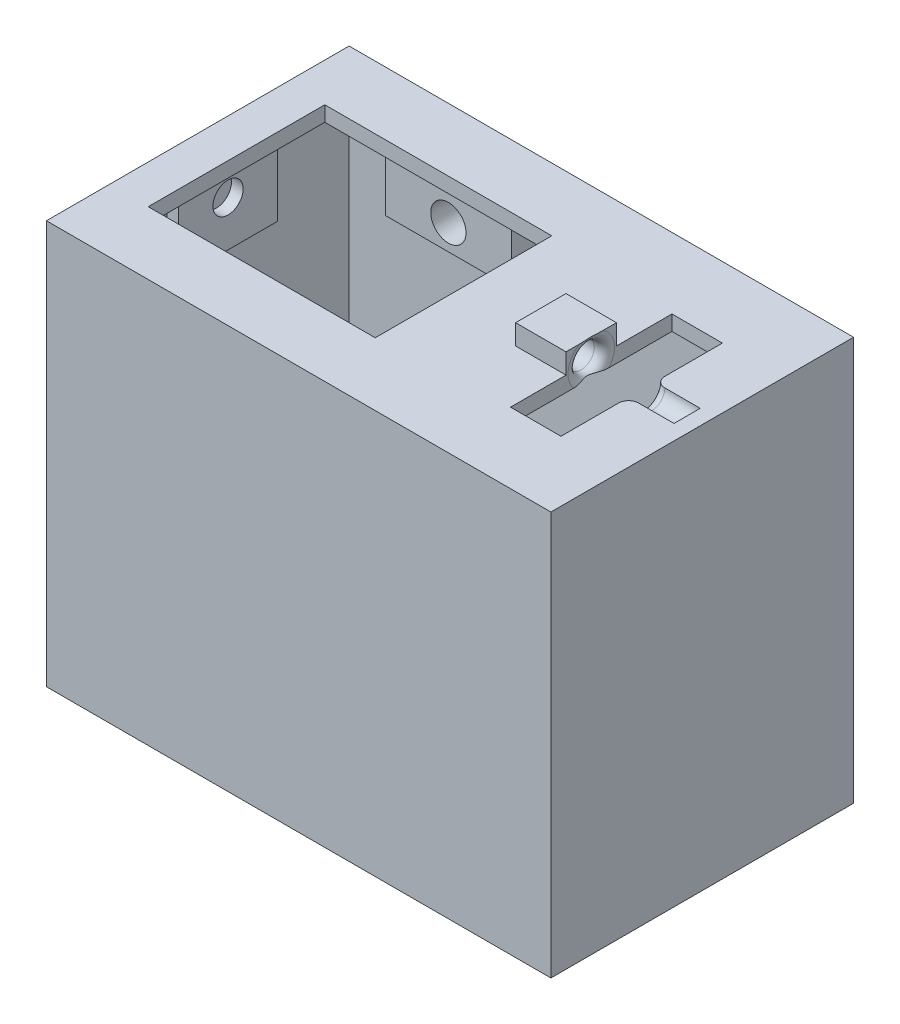
SolidWorks part; units mm, degrees
ref_plane "Front Plane" through (0, 0, 0) normal (0, 0, 1) x (1, 0, 0)
ref_plane "Top Plane" through (0, 0, 0) normal (0, 1, 0) x (1, 0, 0)
ref_plane "Right Plane" through (0, 0, 0) normal (1, 0, 0) x (0, 0, -1)
sketch "Sketch1" plane through (0, 0, 0) normal (0, 1, 0) x (1, 0, 0)
  line L1 (-63.5, -38.1) -> (63.5, -38.1)
  line L2 (-63.5, -38.1) -> (-63.5, 38.1)
  line L3 (-63.5, 38.1) -> (63.5, 38.1)
  line L4 (63.5, -38.1) -> (63.5, 38.1)
  line L5 (-63.5, -38.1) -> (63.5, 38.1) construction
  line L6 (-63.5, 38.1) -> (63.5, -38.1) construction
  point P0 (0, 0)
  dimension "D1" = 127
  dimension "D2" = 76.2
extrude "main body" add sketch "Sketch1" along normal blind 101.6
shell "hollow it" thickness 3.81 removed face at (0, 0, 0)
sketch "Sketch2" plane through (0, 101.6, 0) normal (0, 1, 0) x (1, 0, 0)
  line L0 (63.5, -38.1) -> (63.5, 38.1) construction
  line L1 (48.26, 20.32) -> (35.56, 20.32)
  line L2 (48.26, 20.32) -> (48.26, -20.32)
  line L3 (48.26, -20.32) -> (35.56, -20.32)
  line L4 (35.56, 20.32) -> (35.56, -20.32)
  line L5 (48.26, 20.32) -> (35.56, -20.32) construction
  line L6 (48.26, -20.32) -> (35.56, 20.32) construction
  point P0 (41.91, 0)
  dimension "D1" = 40.64
  dimension "D2" = 12.7
  dimension "D3" = 15.24
extrude "hole for scrollwheel" cut sketch "Sketch2" against normal up to next
ref_plane "arm guys plane" through (35.56, 0, 0) normal (1, 0, 0) x (0, 0, -1)
sketch "Sketch3" plane through (35.56, 0, 0) normal (1, 0, 0) x (0, 0, -1)
  line L0 (0, 101.6) -> (6.35, 101.6)
  line L1 (20.32, 101.6) -> (-20.32, 101.6) construction
  line L2 (6.35, 101.6) -> (6.35, 106.68)
  line L3 (6.35, 106.68) -> (-6.35, 106.68)
  line L4 (-6.35, 106.68) -> (-6.35, 101.6)
  line L5 (-6.35, 101.6) -> (0, 101.6)
  dimension "D1" = 6.35
  dimension "D2" = 6.35
  dimension "D3" = 5.08
extrude "nibble base hole" add sketch "Sketch3" against normal blind 12.7
ref_point "nibble base point"
sketch "Sketch5" plane through (35.56, 0, 0) normal (1, 0, 0) x (0, 0, -1)
  circle A0 centre (0, 101.6) radius 3.302
extrude "nibble hole" cut sketch "Sketch5" against normal blind 11.43 and the other way blind 24.13
fillet "easy to insert scroll wheel" radius 2.54 2 edges at (48.26, 98.298, 0) (35.56, 101.6, 3.302)
sketch "Sketch6" plane through (0, 101.6, 0) normal (0, 1, 0) x (1, 0, 0)
  line L1 (3.4013, 22.225) -> (-53.7487, 22.225)
  line L2 (3.4013, 22.225) -> (3.4013, -22.225)
  line L3 (3.4013, -22.225) -> (-53.7487, -22.225)
  line L4 (-53.7487, 22.225) -> (-53.7487, -22.225)
  line L5 (3.4013, 22.225) -> (-53.7487, -22.225) construction
  line L6 (3.4013, -22.225) -> (-53.7487, 22.225) construction
  point P0 (-25.1737, 0)
  dimension "D1" = 57.15
  dimension "D2" = 44.45
  dimension "D3" = 0
extrude "hole for joystick" cut sketch "Sketch6" against normal blind 11.43
sketch "Sketch10" plane through (0, 97.79, 0) normal (0, -1, 0) x (1, 0, 0)
  line L0 (-59.69, 34.29) -> (59.69, 34.29) construction
  line L1 (-47.3987, 31.75) -> (-2.9487, 31.75)
  line L2 (-47.3987, 31.75) -> (-47.3987, 24.765)
  line L3 (-47.3987, 24.765) -> (-2.9487, 24.765)
  line L4 (-2.9487, 31.75) -> (-2.9487, 24.765)
  line L5 (-47.3987, 31.75) -> (-2.9487, 24.765) construction
  line L6 (-47.3987, 24.765) -> (-2.9487, 31.75) construction
  line L7 (59.69, -34.29) -> (-59.69, -34.29) construction
  line L8 (-41.0487, -31.75) -> (-9.2987, -31.75)
  line L9 (-41.0487, -31.75) -> (-41.0487, -24.765)
  line L10 (-41.0487, -24.765) -> (-9.2987, -24.765)
  line L11 (-9.2987, -31.75) -> (-9.2987, -24.765)
  line L12 (-41.0487, -31.75) -> (-9.2987, -24.765) construction
  line L13 (-41.0487, -24.765) -> (-9.2987, -31.75) construction
  point P0 (-25.1737, 28.2575)
  point P5 (0, 34.29)
  point P10 (-25.1737, -28.2575)
  point P15 (0, -34.29)
  dimension "D1" = 6.35
  dimension "D2" = 6.35
  dimension "D3" = 2.54
  dimension "D4" = 2.54
  dimension "D5" = 2.54
  dimension "D6" = 2.54
extrude "box nibble base" add sketch "Sketch10" along normal blind 15.24
sketch "Sketch11" plane through (0, 97.79, 0) normal (0, -1, 0) x (1, 0, 0)
  line L0 (3.4013, -22.225) -> (3.4013, 22.225) construction
  line L1 (4.6713, -12.4282) -> (9.2433, -12.4282)
  line L2 (4.6713, -12.4282) -> (4.6713, 12.4282)
  line L3 (4.6713, 12.4282) -> (9.2433, 12.4282)
  line L4 (9.2433, -12.4282) -> (9.2433, 12.4282)
  line L5 (4.6713, -12.4282) -> (9.2433, 12.4282) construction
  line L6 (4.6713, 12.4282) -> (9.2433, -12.4282) construction
  line L7 (-53.7487, -22.225) -> (-53.7487, 22.225) construction
  line L8 (-55.88, -12.4282) -> (-58.8287, -12.4282)
  line L9 (-55.88, -12.4282) -> (-55.88, 12.4282)
  line L10 (-55.88, 12.4282) -> (-58.8287, 12.4282)
  line L11 (-58.8287, -12.4282) -> (-58.8287, 12.4282)
  line L12 (-55.88, -12.4282) -> (-58.8287, 12.4282) construction
  line L13 (-55.88, 12.4282) -> (-58.8287, -12.4282) construction
  line L14 (-59.69, -34.29) -> (-59.69, 34.29) construction
  point P0 (6.9573, 0)
  point P5 (3.4013, 0)
  point P8 (-57.3543, 0)
  point P9 (0, 0)
  point P14 (-53.7487, 0)
  point P17 (-59.69, 0)
  dimension "D1" = 1.27
  dimension "D2" = 4.572
  dimension "D3" = 5.08
  dimension "D4" = 3.81
  dimension "D5" = 2.9487
extrude "arch nibble base" add sketch "Sketch11" along normal blind 17.78
sketch "Sketch12" plane through (4.6713, 0, 0) normal (-1, 0, 0) x (0, 0, 1)
  line L1 (-22.225, 97.79) -> (22.225, 97.79) construction
  circle A0 centre (0, 91.44) radius 3.81
  dimension "D2" = 7.62
  dimension "D1" = 6.35
extrude "arch nibble holes" cut sketch "Sketch12" against normal up to surface and the other way up to surface up to face at (9.2433, 88.9, 0) other way up to face at (-59.69, 48.895, 0)
sketch "Sketch13" plane through (0, 0, -24.765) normal (0, 0, 1) x (1, 0, 0)
  line L0 (-9.2987, 82.55) -> (-9.2987, 97.79) construction
  line L1 (-41.0487, 82.55) -> (-41.0487, 97.79) construction
  line L2 (-9.2987, 82.55) -> (-41.0487, 82.55) construction
  circle A0 centre (-25.1737, 88.9) radius 4.445
  point P2 (-9.2987, 90.17)
  point P5 (-41.0487, 90.17)
  point P8 (-25.1737, 82.55)
  dimension "D3" = 8.89
  dimension "D1" = 15.875
  dimension "D2" = 15.875
  dimension "D4" = 6.35
extrude "box nibble holes" cut sketch "Sketch13" against normal up to surface and the other way up to surface up to face at (0, 48.895, -34.29) other way up to face at (0, 48.895, 34.29)
